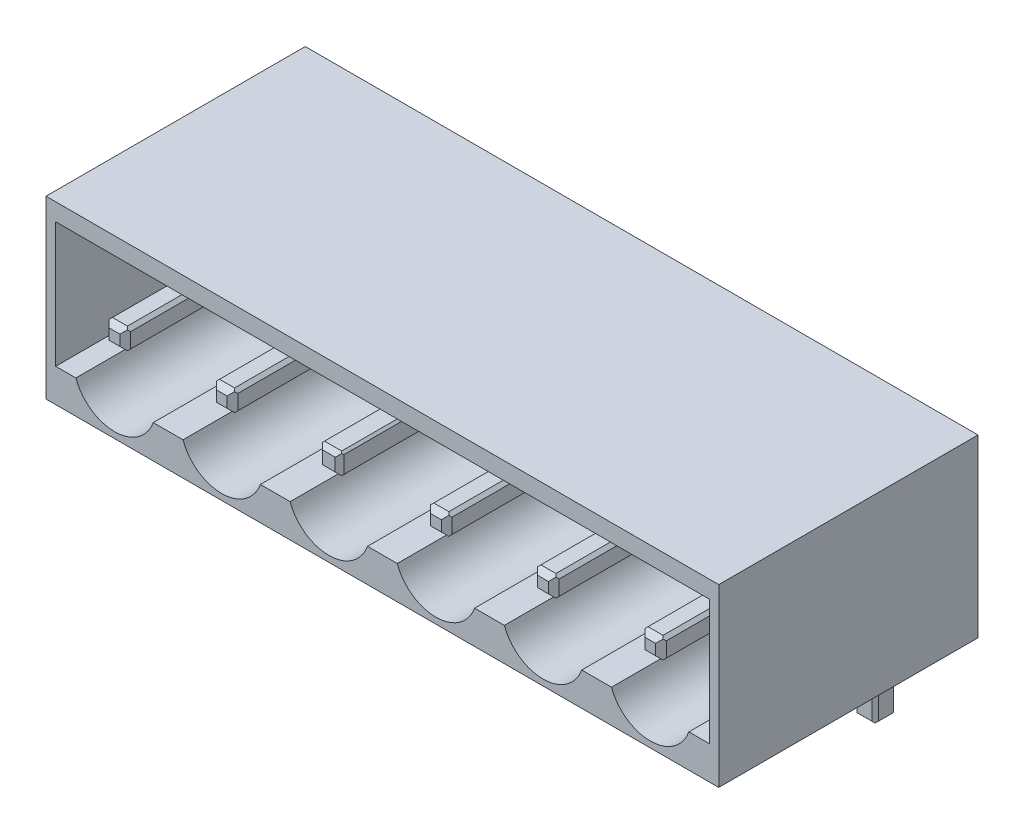
SolidWorks part; units mm, degrees
ref_plane "Спереди" through (0, 0, 0) normal (0, 0, 1) x (1, 0, 0)
ref_plane "Сверху" through (0, 0, 0) normal (0, 1, 0) x (1, 0, 0)
ref_plane "Справа" through (0, 0, 0) normal (1, 0, 0) x (0, 0, -1)
sketch "Эскиз1" plane through (0, 0, 0) normal (0, 0, 1) x (1, 0, 0)
  line L1 (-15.7, 4.1) -> (15.7, 4.1)
  line L2 (-15.7, 4.1) -> (-15.7, -4.1)
  line L3 (-15.7, -4.1) -> (15.7, -4.1)
  line L4 (15.7, 4.1) -> (15.7, -4.1)
  line L5 (-15.7, 4.1) -> (15.7, -4.1) construction
  line L6 (-15.7, -4.1) -> (15.7, 4.1) construction
  point P0 (0, 0)
  dimension "D1" = 8.2
  dimension "D2" = 31.4
extrude "Бобышка-Вытянуть1" add sketch "Эскиз1" along normal blind 12.1
sketch "Эскиз4" plane through (0, 0, 12.1) normal (0, 0, 1) x (1, 0, 0)
  circle A0 centre (-12.5, 0) radius 1.25
  circle A1 centre (-7.5, 0) radius 1.25
  circle A2 centre (-2.5, 0) radius 1.25
  circle A3 centre (2.5, 0) radius 1.25
  circle A4 centre (7.5, 0) radius 1.25
  circle A5 centre (12.5, 0) radius 1.25
  dimension "D1" = 2.5
  dimension "D2" = 3.2
  dimension "D3" = 2
  dimension "D4" = 2
  dimension "D5" = 2
  dimension "D6" = 2
extrude "Вырез-Вытянуть3" cut sketch "Эскиз4" against normal blind 8
sketch "Эскиз5" plane through (0, 0, 12.1) normal (0, 0, 1) x (1, 0, 0)
  line L0 (-15.2456, 0) -> (-15.2456, 3.2929)
  line L1 (-15.2456, 3.2929) -> (-4.7215, 3.2929)
  line L4 (-15.2456, -2.549) -> (-15.2456, 0)
  line L5 (-5.6942, -2.549) -> (-4.3058, -2.549)
  line L6 (-14.3058, -2.549) -> (-15.2456, -2.549)
  line L7 (-10.6942, -2.549) -> (-9.3058, -2.549)
  line L11 (-4.7215, 3.2929) -> (0.2785, 3.2929)
  line L13 (-5.6942, -2.549) -> (-4.3058, -2.549) [skipped]
  line L15 (0.2785, 3.2929) -> (5.2785, 3.2929)
  line L16 (-0.6942, -2.549) -> (0.6942, -2.549)
  line L17 (14.3058, -2.549) -> (15.2785, -2.549)
  line L18 (9.3058, -2.549) -> (10.6942, -2.549)
  line L19 (15.2785, 3.2929) -> (15.2785, -2.549)
  line L20 (4.3058, -2.549) -> (5.6942, -2.549)
  line L21 (5.2785, 3.2929) -> (15.2785, 3.2929)
  arc A1 (-4.3058, -2.549) -> (-0.6942, -2.549) centre (-2.5, -1.9) ccw
  arc A2 (0.6942, -2.549) -> (4.3058, -2.549) centre (2.5, -1.9) ccw
  arc A4 (5.6942, -2.549) -> (9.3058, -2.549) centre (7.5, -1.9) ccw
  arc A5 (-14.3058, -2.549) -> (-10.6942, -2.549) centre (-12.5, -1.9) ccw
  arc A6 (-9.3058, -2.549) -> (-5.6942, -2.549) centre (-7.5, -1.9) ccw
  arc A7 (10.6942, -2.549) -> (14.3058, -2.549) centre (12.5, -1.9) ccw
  dimension "D1" = 3.2
  dimension "D2" = 2.2
  dimension "D3" = 2
  dimension "D4" = 2
  dimension "D5" = 2
  dimension "D6" = 2
extrude "Вырез-Вытянуть4" cut sketch "Эскиз5" against normal blind 7.8
sketch "Эскиз7" plane through (0, 0, 4.1) normal (0, 0, 1) x (1, 0, 0)
  line L0 (-8, 0.5) -> (-7, 0.5)
  line L1 (-13, 0.5) -> (-12, 0.5)
  line L2 (-13, 0.5) -> (-13, -0.5)
  line L3 (-13, -0.5) -> (-12, -0.5)
  line L4 (-12, 0.5) -> (-12, -0.5)
  line L5 (-13, 0.5) -> (-12, -0.5) construction
  line L6 (-13, -0.5) -> (-12, 0.5) construction
  line L7 (-8, 0.5) -> (-8, -0.5)
  line L8 (-8, -0.5) -> (-7, -0.5)
  line L9 (-7, 0.5) -> (-7, -0.5)
  line L10 (-8, 0.5) -> (-7, -0.5) construction
  line L11 (-8, -0.5) -> (-7, 0.5) construction
  line L12 (-3, 0.5) -> (-2, 0.5)
  line L13 (-3, 0.5) -> (-3, -0.5)
  line L14 (-3, -0.5) -> (-2, -0.5)
  line L15 (-2, 0.5) -> (-2, -0.5)
  line L16 (-3, 0.5) -> (-2, -0.5) construction
  line L17 (-3, -0.5) -> (-2, 0.5) construction
  line L18 (2, 0.5) -> (3, 0.5)
  line L19 (2, 0.5) -> (2, -0.5)
  line L20 (2, -0.5) -> (3, -0.5)
  line L21 (3, 0.5) -> (3, -0.5)
  line L22 (2, 0.5) -> (3, -0.5) construction
  line L23 (2, -0.5) -> (3, 0.5) construction
  line L24 (7, 0.5) -> (8, 0.5)
  line L25 (7, 0.5) -> (7, -0.5)
  line L26 (7, -0.5) -> (8, -0.5)
  line L27 (8, 0.5) -> (8, -0.5)
  line L28 (12, 0.5) -> (13, 0.5)
  line L29 (12, 0.5) -> (12, -0.5)
  line L30 (12, -0.5) -> (13, -0.5)
  line L31 (13, 0.5) -> (13, -0.5)
  line L32 (7, 0.5) -> (8, -0.5) construction
  line L33 (7, -0.5) -> (8, 0.5) construction
  line L34 (12, 0.5) -> (13, -0.5) construction
  line L35 (12, -0.5) -> (13, 0.5) construction
  point P0 (-12.5, 0)
  point P7 (-7.5, 0)
  point P12 (-2.5, 0)
  point P17 (2.5, 0)
  point P23 (7.5, 0)
  point P28 (12.5, 0)
  dimension "D1" = 1
  dimension "D2" = 1
  dimension "D3" = 2
  dimension "D4" = 2
  dimension "D5" = 2
  dimension "D6" = 2
extrude "Бобышка-Вытянуть2" add sketch "Эскиз7" along normal blind 8
chamfer "Фаска1" distance 0.15 angle 45 16 edges at (-8, -0.5, 8.1) (-8, 0.5, 8.1) (-7, 0.5, 8.1) (-7, -0.5, 8.1) (-12, -0.5, 8.1) (-12, 0.5, 8.1) (-13, -0.5, 8.1) (-13, 0.5, 8.1) (13, -0.5, 8.1) (8, -0.5, 8.1) (13, 0.5, 8.1) (12, -0.5, 8.1) (12, 0.5, 8.1) (8, 0.5, 8.1) (7, -0.5, 8.1) (7, 0.5, 8.1)
chamfer "Фаска2" distance 0.25 angle 45 16 edges at (-8, 0, 12.1) (-7.5, 0.5, 12.1) (-7, 0, 12.1) (-7.5, -0.5, 12.1) (-12, 0, 12.1) (-12.5, -0.5, 12.1) (-13, 0, 12.1) (-12.5, 0.5, 12.1) (13, 0, 12.1) (12.5, -0.5, 12.1) (12.5, 0.5, 12.1) (12, 0, 12.1) (8, 0, 12.1) (7.5, -0.5, 12.1) (7, 0, 12.1) (7.5, 0.5, 12.1)
sketch "Эскиз8" plane through (0, -4.1, 0) normal (0, -1, 0) x (-1, 0, 0)
  line L0 (8, -2.1) -> (7, -2.1)
  line L1 (13, -2.1) -> (12, -2.1)
  line L2 (13, -2.1) -> (13, -1.1)
  line L3 (13, -1.1) -> (12, -1.1)
  line L4 (12, -2.1) -> (12, -1.1)
  line L5 (13, -2.1) -> (12, -1.1) construction
  line L6 (13, -1.1) -> (12, -2.1) construction
  line L7 (8, -2.1) -> (8, -1.1)
  line L8 (8, -1.1) -> (7, -1.1)
  line L9 (7, -2.1) -> (7, -1.1)
  line L10 (8, -2.1) -> (7, -1.1) construction
  line L11 (8, -1.1) -> (7, -2.1) construction
  line L12 (3, -2.1) -> (2, -2.1)
  line L13 (3, -2.1) -> (3, -1.1)
  line L14 (3, -1.1) -> (2, -1.1)
  line L15 (2, -2.1) -> (2, -1.1)
  line L16 (3, -2.1) -> (2, -1.1) construction
  line L17 (3, -1.1) -> (2, -2.1) construction
  line L18 (-2, -2.1) -> (-3, -2.1)
  line L19 (-2, -2.1) -> (-2, -1.1)
  line L20 (-2, -1.1) -> (-3, -1.1)
  line L21 (-3, -2.1) -> (-3, -1.1)
  line L22 (-2, -2.1) -> (-3, -1.1) construction
  line L23 (-2, -1.1) -> (-3, -2.1) construction
  line L24 (-7, -2.1) -> (-8, -2.1)
  line L25 (-7, -2.1) -> (-7, -1.1)
  line L26 (-7, -1.1) -> (-8, -1.1)
  line L27 (-8, -2.1) -> (-8, -1.1)
  line L28 (-12, -2.1) -> (-13, -2.1)
  line L29 (-12, -2.1) -> (-12, -1.1)
  line L30 (-12, -1.1) -> (-13, -1.1)
  line L31 (-13, -2.1) -> (-13, -1.1)
  line L32 (-7, -2.1) -> (-8, -1.1) construction
  line L33 (-7, -1.1) -> (-8, -2.1) construction
  line L34 (-12, -2.1) -> (-13, -1.1) construction
  line L35 (-12, -1.1) -> (-13, -2.1) construction
  point P0 (12.5, -1.6)
  point P7 (7.5, -1.6)
  point P12 (2.5, -1.6)
  point P17 (-2.5, -1.6)
  point P22 (-7.5, -1.6)
  point P27 (-12.5, -1.6)
  dimension "D1" = 1
  dimension "D2" = 1
  dimension "D3" = 3.2
  dimension "D4" = 1.6
  dimension "D5" = 2
  dimension "D6" = 2
  dimension "D7" = 2
  dimension "D8" = 2
extrude "Бобышка-Вытянуть3" add sketch "Эскиз8" along normal blind 4
chamfer "Фаска3" distance 0.15 angle 45 24 edges at (-12, -6.1, 1.1) (-7, -6.1, 1.1) (-13, -6.1, 1.1) (-12, -6.1, 2.1) (-7, -6.1, 2.1) (-8, -6.1, 1.1) (-8, -6.1, 2.1) (-13, -6.1, 2.1) (3, -0.5, 8.1) (2, -0.5, 8.1) (3, 0.5, 8.1) (2, 0.5, 8.1) (3, -6.1, 1.1) (3, -6.1, 2.1) (2, -6.1, 1.1) (2, -6.1, 2.1) (8, -6.1, 1.1) (13, -6.1, 1.1) (13, -6.1, 2.1) (12, -6.1, 1.1) (12, -6.1, 2.1) (8, -6.1, 2.1) (7, -6.1, 1.1) (7, -6.1, 2.1)
chamfer "Фаска4" distance 0.25 angle 45 24 edges at (-7, -8.1, 1.6) (-8, -8.1, 1.6) (-7.5, -8.1, 2.1) (-7.5, -8.1, 1.1) (-13, -8.1, 1.6) (-12.5, -8.1, 2.1) (-12, -8.1, 1.6) (-12.5, -8.1, 1.1) (2.5, -8.1, 1.1) (2, -8.1, 1.6) (2.5, -8.1, 2.1) (3, -8.1, 1.6) (2.5, -0.5, 12.1) (2, 0, 12.1) (3, 0, 12.1) (2.5, 0.5, 12.1) (12, -8.1, 1.6) (12.5, -8.1, 1.1) (13, -8.1, 1.6) (12.5, -8.1, 2.1) (8, -8.1, 1.6) (7.5, -8.1, 1.1) (7, -8.1, 1.6) (7.5, -8.1, 2.1)
chamfer "Фаска6" distance 0.1 angle 45 4 edges at (-3, -0.5, 8.1) (-2, -0.5, 8.1) (-2, 0.5, 8.1) (-3, 0.5, 8.1)
chamfer "Фаска7" distance 0.2 angle 45 4 edges at (-2, 0, 12.1) (-2.5, -0.5, 12.1) (-3, 0, 12.1) (-2.5, 0.5, 12.1)
chamfer "Фаска8" distance 0.1 angle 45 4 edges at (-3, -6.1, 1.1) (-2, -6.1, 1.1) (-3, -6.1, 2.1) (-2, -6.1, 2.1)
chamfer "Фаска9" distance 0.2 angle 45 4 edges at (-2, -8.1, 1.6) (-2.5, -8.1, 1.1) (-3, -8.1, 1.6) (-2.5, -8.1, 2.1)
